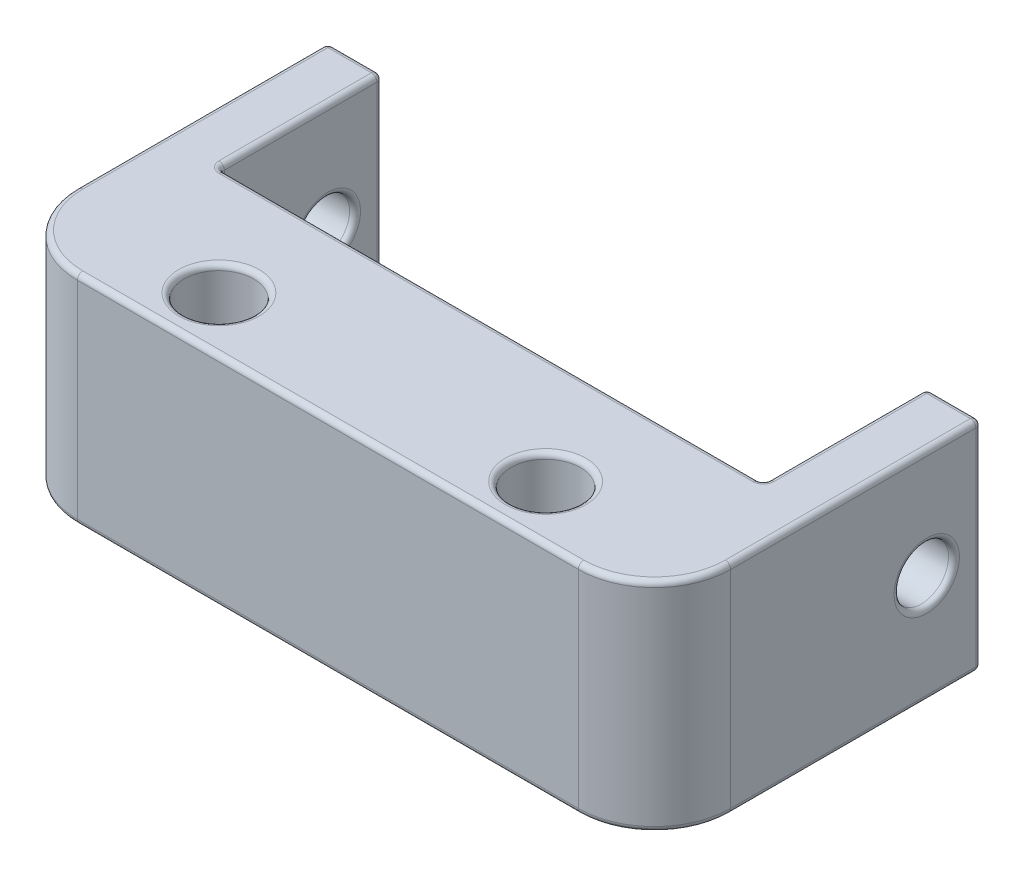
SolidWorks part; units mm, degrees
ref_plane "Front Plane" through (0, 0, 0) normal (0, 0, 1) x (1, 0, 0)
ref_plane "Top Plane" through (0, 0, 0) normal (0, 1, 0) x (1, 0, 0)
ref_plane "Right Plane" through (0, 0, 0) normal (1, 0, 0) x (0, 0, -1)
sketch "Sketch1" plane through (0, 0, 0) normal (0, 1, 0) x (1, 0, 0)
  line L0 (-25, -5) -> (-25, 10)
  line L1 (-30, -10) -> (30, -10)
  line L2 (-30, -10) -> (-30, 10)
  line L3 (-30, 10) -> (30, 10)
  line L4 (30, -10) -> (30, 10)
  line L5 (-30, -10) -> (30, 10) construction
  line L6 (-30, 10) -> (30, -10) construction
  line L8 (25, -5) -> (25, 10)
  line L9 (-25, -5) -> (25, -5)
  line L10 (-25, 5) -> (25, 5) construction
  line L11 (-25, -5) -> (-25, 5) construction
  line L12 (25, -5) -> (25, 5) construction
  line L13 (-30, -11.5) -> (30, -11.5) construction
  line L14 (-30, -10) -> (30, -10)
  line L15 (-30, -10) -> (-30, -13)
  line L16 (-23, -20) -> (23, -20)
  line L17 (30, -10) -> (30, -13)
  line L18 (-30, -20) -> (0, -20) construction
  line L19 (0, -20) -> (0, 10) construction
  circle A0 centre (-15, -15) radius 3.2
  circle A1 centre (15, -15) radius 3.2
  arc A2 (23, -20) -> (30, -13) centre (23, -13) ccw
  arc A3 (-30, -13) -> (-23, -20) centre (-23, -13) ccw
  point P0 (0, 0)
  point P19 (-15, -15)
  dimension "D5" = 6.4
  dimension "D6" = 7
  dimension "D1" = 20
  dimension "D2" = 60
  dimension "D4" = 10
  dimension "D3" = 5
extrude "Boss-Extrude1" add sketch "Sketch1" along normal blind 20 contours L9 L0 L3 L2 L1 L4 L8 | L15 A3 L16 A2 L17 L1 A1 A0 region at (0, 0, 5.6325) region at (0, 0, 14.8596)
sketch "Sketch2" plane through (-30, 0, 0) normal (-1, 0, 0) x (0, 0, 1)
  line L0 (-10, 10) -> (-5, 10) construction
  line L1 (-10, 20) -> (-10, 0) construction
  circle A0 centre (-5, 10) radius 2.5
  dimension "D2" = 5
  dimension "D1" = 5
extrude "Cut-Extrude1" cut sketch "Sketch2" against normal blind 70
fillet "Fillet1" radius 0.5 34 edges at (25, 10, 5) (-15, 0, 18.2) (15, 0, 18.2) (-27.9497, 0, 17.9497) (0, 0, 20) (27.9497, 0, 17.9497) (25, 0, -2.5) (0, 0, 5) (30, 0, 1.5) (30, 10, -2.5) (-25, 10, 5) (-25, 0, -2.5) (-25, 10, -2.5) (-25, 10, -10) (-27.5, 0, -10) (-30, 10, -10) (-30, 0, 1.5) (-30, 10, -2.5) (30, 10, -10) (25, 10, -10) (27.5, 0, -10) (-15, 20, 18.2) (15, 20, 18.2) (25, 20, -2.5) (27.5, 20, -10) (30, 20, 1.5) (27.9497, 20, 17.9497) (0, 20, 20) (-27.9497, 20, 17.9497) (-30, 20, 1.5) (-27.5, 20, -10) (-25, 20, -2.5) (0, 20, 5) (25, 10, -2.5)
